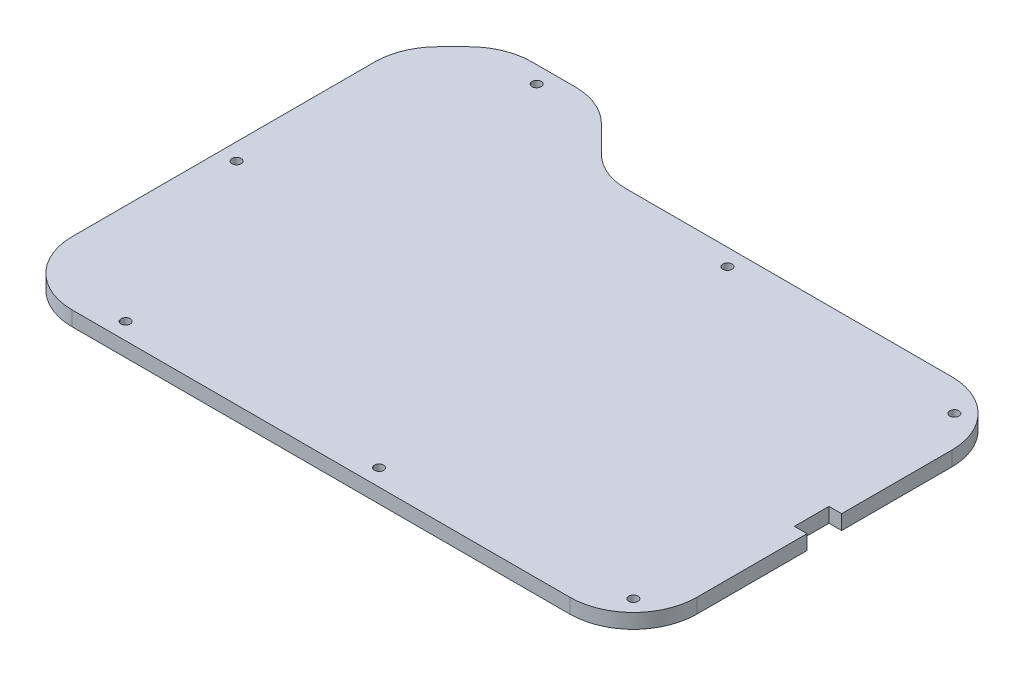
SolidWorks part; units mm, degrees
ref_plane "Front Plane" through (0, 0, 0) normal (0, 0, 1) x (1, 0, 0)
ref_plane "Top Plane" through (0, 0, 0) normal (0, 1, 0) x (1, 0, 0)
ref_plane "Right Plane" through (0, 0, 0) normal (1, 0, 0) x (0, 0, -1)
sketch "Sketch1" plane through (0, 0, 0) normal (0, 1, 0) x (1, 0, 0)
  line L30 (-37.2211, -95.1196) -> (-37.2211, -39.8196) construction
  line L31 (-51.0711, -25.9696) -> (-121.754, -25.9696) construction
  line L32 (-130.7342, -22.2498) -> (-136.5579, -16.4261) construction
  line L33 (-146.3513, -12.3696) -> (-155.7143, -12.3696) construction
  line L34 (-165.5078, -16.4261) -> (-168.788, -19.7064) construction
  line L35 (-172.8446, -29.4998) -> (-172.8446, -95.1196) construction
  line L36 (-158.9946, -108.9696) -> (-51.0711, -108.9696) construction
  line L37 (-37.3211, -95.1196) -> (-37.3211, -71.2196)
  line L38 (-51.0711, -26.0696) -> (-121.754, -26.0696)
  line L39 (-130.8049, -22.3205) -> (-136.6286, -16.4968)
  line L40 (-146.3513, -12.4696) -> (-155.7143, -12.4696)
  line L41 (-165.437, -16.4968) -> (-168.7173, -19.7771)
  line L42 (-172.7446, -29.4998) -> (-172.7446, -95.1196)
  line L43 (-158.9946, -108.8696) -> (-51.0711, -108.8696)
  line L44 (-37.3211, -67.4696) -> (-40.0711, -67.4696) construction
  line L45 (-40.0711, -71.2196) -> (-40.0711, -63.7196)
  line L46 (-40.0711, -63.7196) -> (-37.3211, -63.7196)
  line L47 (-40.0711, -71.2196) -> (-37.3211, -71.2196)
  line L48 (-37.3211, -63.7196) -> (-37.3211, -39.8196)
  line L49 (-37.3211, -95.1196) -> (-37.3211, -39.8196) construction
  line L50 (-37.3211, -63.7196) -> (-37.3211, -71.2196) construction
  arc A50 (-51.0711, -108.9696) -> (-37.2211, -95.1196) centre (-51.0711, -95.1196) ccw construction
  arc A51 (-37.2211, -39.8196) -> (-51.0711, -25.9696) centre (-51.0711, -39.8196) ccw construction
  arc A52 (-130.7342, -22.2498) -> (-121.754, -25.9696) centre (-121.754, -13.2696) ccw construction
  arc A53 (-136.5579, -16.4261) -> (-146.3513, -12.3696) centre (-146.3513, -26.2196) ccw construction
  arc A54 (-155.7143, -12.3696) -> (-165.5078, -16.4261) centre (-155.7143, -26.2196) ccw construction
  arc A55 (-168.788, -19.7064) -> (-172.8446, -29.4998) centre (-158.9946, -29.4998) ccw construction
  arc A56 (-172.8446, -95.1196) -> (-158.9946, -108.9696) centre (-158.9946, -95.1196) ccw construction
  circle A57 centre (-169.0946, -63.1097) radius 1
  circle A58 centre (-151.0328, -16.1196) radius 1
  circle A59 centre (-96.0754, -29.7196) radius 1
  circle A60 centre (-43.9293, -32.6778) radius 1
  circle A61 centre (-43.9293, -102.2613) radius 1
  circle A62 centre (-96.0754, -105.2196) radius 1
  circle A63 centre (-151.0328, -105.2196) radius 1
  arc A64 (-37.3211, -39.8196) -> (-51.0711, -26.0696) centre (-51.0711, -39.8196) ccw
  arc A65 (-130.8049, -22.3205) -> (-121.754, -26.0696) centre (-121.754, -13.2696) ccw
  arc A66 (-136.6286, -16.4968) -> (-146.3513, -12.4696) centre (-146.3513, -26.2196) ccw
  arc A67 (-155.7143, -12.4696) -> (-165.437, -16.4968) centre (-155.7143, -26.2196) ccw
  arc A68 (-168.7173, -19.7771) -> (-172.7446, -29.4998) centre (-158.9946, -29.4998) ccw
  arc A69 (-172.7446, -95.1196) -> (-158.9946, -108.8696) centre (-158.9946, -95.1196) ccw
  arc A70 (-51.0711, -108.8696) -> (-37.3211, -95.1196) centre (-51.0711, -95.1196) ccw
  point P61 (-40.0711, -67.4696)
  dimension "D1" = 0.1
extrude "Boss-Extrude1" add sketch "Sketch1" along normal blind 3.175
